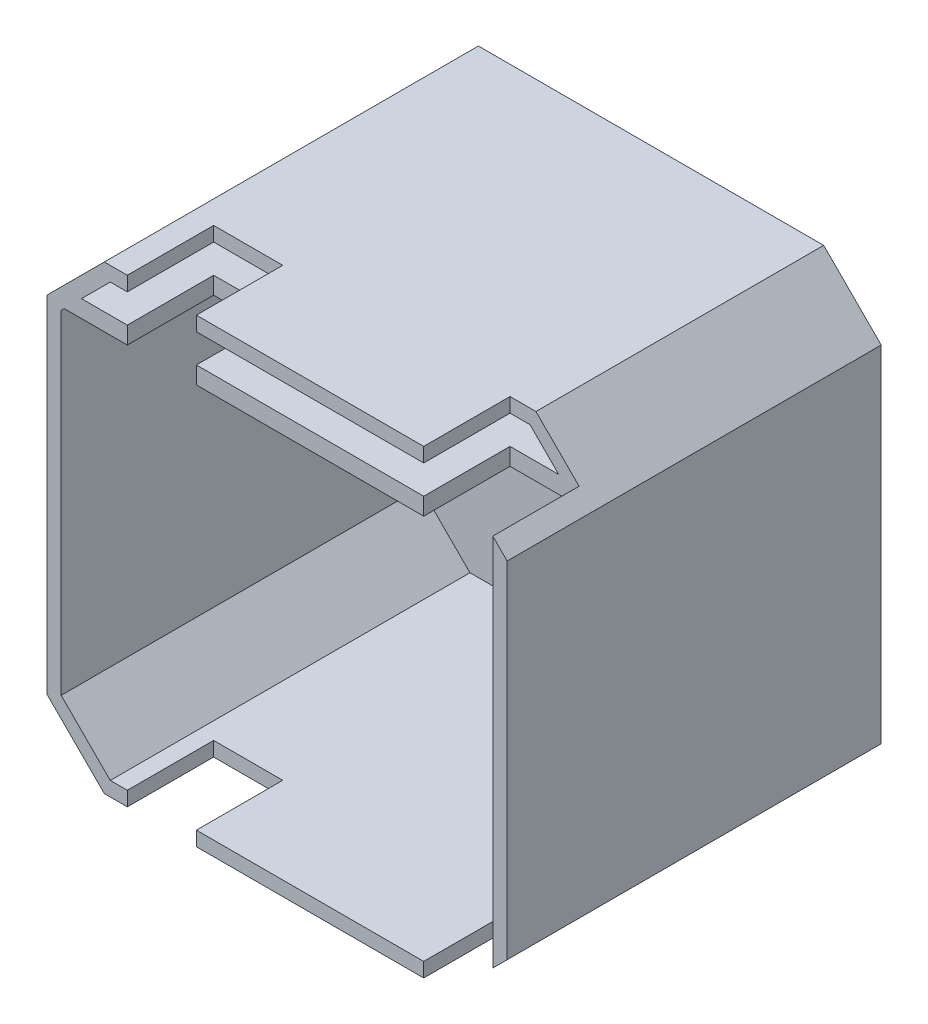
SolidWorks part; units mm, degrees
ref_plane "Front Plane" through (0, 0, 0) normal (0, 0, 1) x (1, 0, 0)
ref_plane "Top Plane" through (0, 0, 0) normal (0, 1, 0) x (1, 0, 0)
ref_plane "Right Plane" through (0, 0, 0) normal (1, 0, 0) x (0, 0, -1)
sketch "Sketch1" plane through (0, 0, 0) normal (0, 0, 1) x (1, 0, 0)
  line L0 (-40, 30) -> (-30, 40)
  line L1 (-30, -40) -> (30, -40)
  line L2 (-40, -30) -> (-40, 30)
  line L3 (-30, 40) -> (30, 40)
  line L4 (40, -30) -> (40, 30)
  line L5 (-35, -35) -> (35, 35) construction
  line L6 (-40, 40) -> (35, -35) construction
  line L7 (30, 40) -> (40, 30)
  line L8 (40, -30) -> (30, -40)
  line L9 (-30, -40) -> (-40, -30)
  line L10 (-37.5, 28.9645) -> (-28.9645, 37.5)
  line L11 (-28.9645, 37.5) -> (28.9645, 37.5)
  line L12 (28.9645, 37.5) -> (37.5, 28.9645)
  line L13 (37.5, -28.9645) -> (37.5, 28.9645)
  line L14 (37.5, -28.9645) -> (28.9645, -37.5)
  line L15 (-28.9645, -37.5) -> (28.9645, -37.5)
  line L16 (-28.9645, -37.5) -> (-37.5, -28.9645)
  line L17 (-37.5, -28.9645) -> (-37.5, 28.9645)
  line L18 (55, 0) -> (-55, 0) construction
  point P0 (0, 0)
  point P17 (0, 0)
  dimension "D1" = 2.5
  dimension "D2" = 80
  dimension "D4" = 40
  dimension "D3" = 4
extrude "Boss-Extrude1" add sketch "Sketch1" along normal blind 65
sketch "Sketch2" plane through (0, 0, 0) normal (0, 0, 1) x (1, 0, 0)
  line L0 (37.5, 28.9645) -> (28.9645, 37.5)
  line L1 (28.9645, 37.5) -> (-28.9645, 37.5)
  line L2 (-28.9645, 37.5) -> (-37.5, 28.9645)
  line L3 (-37.5, 28.9645) -> (-37.5, -28.9645)
  line L4 (-37.5, -28.9645) -> (-28.9645, -37.5)
  line L5 (-28.9645, -37.5) -> (28.9645, -37.5)
  line L6 (28.9645, -37.5) -> (37.5, -28.9645)
  line L7 (37.5, -28.9645) -> (37.5, 28.9645)
  circle A0 centre (0, 0) radius 7.5
  dimension "D1" = 15
extrude "Boss-Extrude2" add sketch "Sketch2" along normal blind 2.5
sketch "Sketch3" plane through (0, 0, 0) normal (1, 0, 0) x (0, 0, -1)
  line L0 (0, 44) -> (0, -44) construction
  line L1 (-65, 32.5) -> (0, 32.5)
  line L2 (-65, 32.5) -> (-65, 29.5)
  line L3 (-65, 29.5) -> (0, 29.5)
  line L4 (0, 32.5) -> (0, 29.5)
  line L6 (-65, 37.5) -> (-2.5, 37.5) construction
  line L7 (-65, 30) -> (-65, 40) construction
  point P7 (-65, 30)
  point P8 (0, 0)
  point P9 (0, 0)
  point P10 (0, 0)
  point P11 (0, 0)
  point P12 (0, 0)
  point P13 (-65.4146, 32.3568)
  point P15 (0, 0)
  point P17 (-65, 32.5)
  dimension "D1" = 3
  dimension "D2" = 5
extrude "Boss-Extrude3" add sketch "Sketch3" along normal up to next and the other way up to next
sketch "Sketch5" plane through (0, 0, 65) normal (0, 0, 1) x (1, 0, 0)
  line L0 (-36.9645, 29.5) -> (36.9645, 29.5) construction
  line L1 (7.5, 29.5) -> (-37.5, 29.5)
  line L2 (7.5, 29.5) -> (7.5, 32.5)
  line L3 (7.5, 32.5) -> (-37.5, 32.5)
  line L4 (-37.5, 29.5) -> (-37.5, 32.5)
  line L6 (-37.5, 28.9645) -> (-37.5, -28.9645) construction
  line L7 (-33.9645, 32.5) -> (33.9645, 32.5) construction
  dimension "D1" = 45
extrude "Boss-Extrude4" [suppressed] add sketch "Sketch5" along normal blind 12.5
sketch "Sketch4" [suppressed] plane through (0, 27, 0) normal (0, -1, 0) x (1, 0, 0)
  line L1 (-37.5, 2.5) -> (-37.5, 50) construction
  line L2 (-37.5, 62.5) -> (7.5, 62.5) construction
  circle A0 centre (-27.5, 22.5) radius 1.75
  circle A1 centre (2.5, 57.5) radius 1.75
  dimension "D1" = 3.5
  dimension "D2" = 3.5
  dimension "D3" = 30
  dimension "D4" = 35
  dimension "D5" = 5
  dimension "D6" = 10
extrude "Cut-Extrude1" [suppressed] cut sketch "Sketch4" against normal up to next
sketch "Sketch6" plane through (0, 29.5, -27) normal (0, -1, 0) x (-1, 0, 0)
  line L1 (-36.9645, -29.5) -> (36.9645, -29.5) construction
  line L3 (37.5, -29.5) -> (37.5, -92) construction
  circle A0 centre (0, -72) radius 1.75
  circle A1 centre (30, -37) radius 1.75
  dimension "D1" = 3.5
  dimension "D2" = 3.5
  dimension "D3" = 30
  dimension "D4" = 35
  dimension "D5" = 7.5
  dimension "D6" = 7.5
extrude "Cut-Extrude2" cut sketch "Sketch6" against normal up to next
sketch "Sketch7" plane through (0, 0, 2.5) normal (0, 0, 1) x (1, 0, 0)
  line L0 (-33.9645, 32.5) -> (-28.9645, 37.5)
  line L1 (-28.9645, 37.5) -> (-33.9645, 32.5) construction
  line L2 (-28.9645, 37.5) -> (28.9645, 37.5)
  line L3 (28.9645, 37.5) -> (33.9645, 32.5)
  line L4 (33.9645, 32.5) -> (-33.9645, 32.5)
extrude "Cut-Extrude3" cut sketch "Sketch7" against normal up to next
sketch "Sketch8" plane through (0, 0, 2.5) normal (0, 0, 1) x (1, 0, 0)
  line L6 (-15, 10.5) -> (-15, 3.3963) construction
  line L7 (-36.9645, 29.5) -> (36.9645, 29.5) construction
  line L9 (-5, 7.5) -> (0, 7.5)
  line L10 (0, 7.5) -> (-7.5, 0)
  line L11 (35.75, 0) -> (-35.75, 0) construction
  line L13 (-25, 19.5) -> (-5, 19.5)
  line L14 (-25, 19.5) -> (-25, 10.5)
  line L15 (-25, 10.5) -> (-15, 10.5)
  line L16 (-5, 19.5) -> (-5, 7.5)
  line L18 (-19.75, 12.86) -> (-10.25, 12.86) construction
  circle A0 centre (0, 0) radius 7.5 construction
  circle A1 centre (0, 0) radius 7.5 construction
  arc A2 (-15, 10.5) -> (-7.5, 0) centre (-14.75, 2.75) cw
  point P16 (-15, 12.86)
  dimension "D1" = 10
  dimension "D2" = 10
  dimension "D3" = 0
  dimension "D6" = 20
  dimension "D7" = 9
extrude "Cut-Extrude4" cut sketch "Sketch8" against normal up to next
fillet "Fillet1" radius 2.5 3 edges at (-5, 19.5, 1.25) (-25, 19.5, 1.25) (-25, 10.5, 1.25)
fillet "Fillet2" radius 5 1 edges at (-5, 7.5, 1.25)
sketch "Sketch9" plane through (0, 40, 0) normal (0, 1, 0) x (1, 0, 0)
  line L0 (40, -65) -> (40, 0) construction
  line L1 (25.5, -50) -> (37.5, -50)
  line L2 (25.5, -50) -> (25.5, -82.9492)
  line L3 (25.5, -82.9492) -> (37.5, -82.9492)
  line L4 (37.5, -50) -> (37.5, -82.9492)
  line L5 (30, -65) -> (-30, -65) construction
  line L6 (-26, -50) -> (-14, -50)
  line L7 (-26, -50) -> (-26, -67.9492)
  line L8 (-26, -67.9492) -> (-14, -67.9492)
  line L9 (-14, -50) -> (-14, -67.9492)
  line L10 (-40, -65) -> (-40, 0) construction
  point P12 (-13.8213, -35)
  dimension "D1" = 2.5
  dimension "D2" = 12
  dimension "D3" = 15
  dimension "D4" = 14
extrude "Cut-Extrude5" cut sketch "Sketch9" against normal through all both and the other way through all
